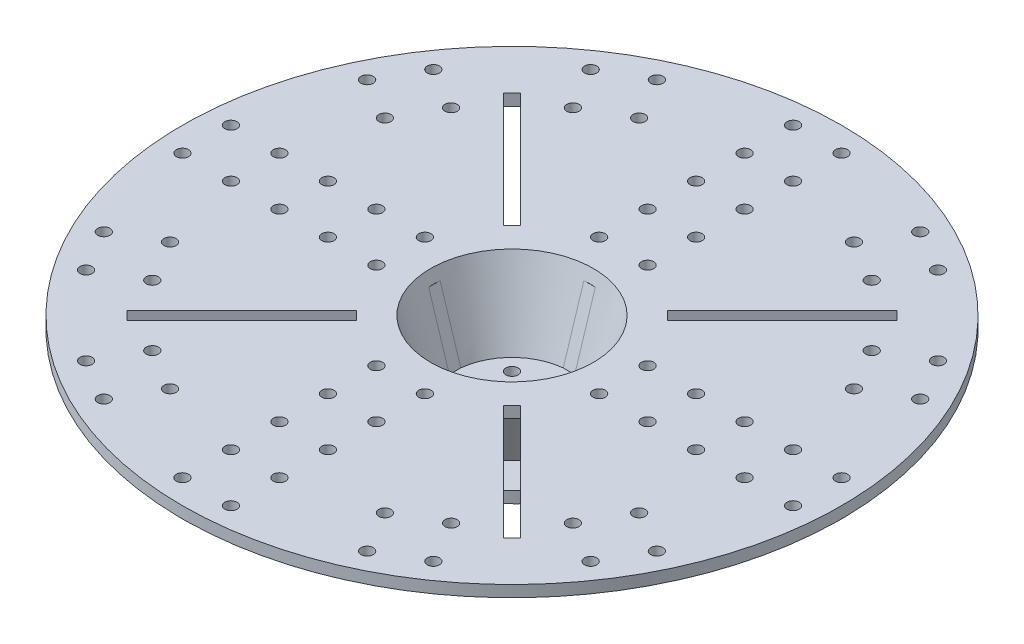
SolidWorks part; units mm, degrees
note: '?' marks a value the reader was unsure of.
material "ULTEM 9085"
ref_plane "Front Plane" through (0, 0, 0) normal (0, 0, 1) x (1, 0, 0)
ref_plane "Top Plane" through (0, 0, 0) normal (0, 1, 0) x (1, 0, 0)
ref_plane "Right Plane" through (0, 0, 0) normal (1, 0, 0) x (0, 0, -1)
other "Center of Mass"
sketch "Sketch1" plane through (0, 0, 0) normal (0, 0, 1) x (1, 0, 0)
  line L0 (0, -40.25) -> (0, -46.25)
  line L1 (0, -40.25) -> (30, -40.25)
  line L2 (30, -40.25) -> (42.6498, 0)
  line L3 (42.6498, 0) -> (172.6498, 0)
  line L4 (105.9574, 0) -> (-105.9574, 0) construction
  line L5 (172.6498, 0) -> (172.6498, -6)
  line L6 (42.6498, 0) -> (42.6498, -31.4331) construction
  line L7 (172.6498, -6) -> (46.8968, -6)
  line L8 (36.1179, -40.2971) -> (46.8968, -6)
  line L9 (36.1179, -40.2971) -> (55.5, -40.2971)
  line L10 (55.5, -40.2971) -> (55.5, -46.25)
  line L11 (55.5, -46.25) -> (0, -46.25)
  line L12 (0, -25.4375) -> (0, 25.4375) construction
  point P15 (0, -43.25)
  point P16 (55.5, -43.2736)
  point P24 (36.3249, -20.125)
  point P25 (41.5074, -23.1486)
  dimension "D1" = 72.553
  dimension "D2" = 30
  dimension "D3" = 130
  dimension "D4" = 6
  dimension "D5" = 6
  dimension "D6" = 55.5
  dimension "D7" = 34.2971
  dimension "D8" = 40.25
  dimension "D9" = 6
revolve "Revolve2" add sketch "Sketch1" angle 360 about L0
ref_axis "Axis1" through (0, 0, 0) along (0, -1, 0)?
sketch "Sketch3" plane through (0, 0, 0) normal (0, 0, 1) x (1, 0, 0)
  line L0 (55.5, -40.2971) -> (172.6498, -6)
  line L1 (172.6498, -6) -> (0, -6)
  line L2 (-172.6498, -6) -> (172.6498, -6) construction
  line L3 (0, -6) -> (0, -40.2971)
  line L4 (55.5, -40.2971) -> (-55.5, -40.2971) construction
  line L5 (0, -40.2971) -> (55.5, -40.2971)
extrude "Boss-Extrude2" add sketch "Sketch3" along normal mid plane 6
pattern_circular "CirPattern2" count 4 over 360 about axis through (0, 0, 0) along (0, 1, 0) of "Boss-Extrude2"
sketch "Sketch6" plane through (0, 0, 3) normal (0, 0, 1) x (1, 0, 0)
  line L0 (-3, -6) -> (-40.6536, -6)
  line L1 (-40.6536, -6) -> (-29.8496, -40.25)
  line L2 (-29.8496, -40.25) -> (-3, -40.25)
  line L3 (-3, -40.25) -> (-3, -6)
  spline S0 degree 3 poles (-29.8496, -40.25) (-33.4553, -28.8347) (-37.0555, -17.4177) (-40.6536, -6) knots 0 0 0 0 1 1 1 1 construction
extrude "Cut-Extrude3" cut sketch "Sketch6" against normal blind 6
pattern_circular "CirPattern4" count 4 over 360 about axis through (0, 0, 0) along (0, 1, 0) of "Cut-Extrude3"
sketch "Sketch7" plane through (0, -6, 0) normal (0, 1, 0) x (1, 0, 0)
  line L0 (-3, 3) -> (-3, -3)
  line L1 (-3, -3) -> (3, -3)
  line L2 (-3, -3) -> (3, -3) construction
  line L3 (3, -3) -> (3, 3)
  line L4 (3, 3) -> (-3, 3) construction
  line L5 (3, 3) -> (-3, 3)
extrude "Cut-Extrude4" cut sketch "Sketch7" against normal up to surface (34.25 mm away) up to face at (0, -40.25, 0)
sketch "Sketch8" plane through (0, -40.25, 0) normal (0, 1, 0) x (1, 0, 0)
  circle A0 centre (0, 0) radius 3.175
  dimension "D1" = 6.35
extrude "Cut-Extrude5" cut sketch "Sketch8" against normal through all
sketch "Sketch11" plane through (0, -6, 0) normal (0, -1, 0) x (1, 0, 0)
  line L0 (0, -25.4375) -> (0, 25.4375) construction
  circle A0 centre (-12.7, 159.9498) radius 3.2
  arc A2 (3, 172.6237) -> (0, 172.6498) centre (0, 0) ccw construction
  point P9 (0, 172.6498)
  dimension "D1" = 6.4
  dimension "D2" = 12.7
  dimension "D3" = 12.7
extrude "Cut-Extrude6" cut sketch "Sketch11" against normal through all
pattern_linear "LPattern2" count 2 spacing 25.4 along (1, 0, 0) count 6 spacing 25.4 along (0, 0, -1) of "Cut-Extrude6"
pattern_circular "CirPattern5" count 4 over 360 about axis through (0, 0, 0) along (0, 1, 0) of "LPattern2", "Cut-Extrude6"
sketch "Sketch12" plane through (0, 0, 0) normal (0, 1, 0) x (1, 0, 0)
  line L0 (0, 0) -> (-149.5191, -86.3249) construction
  line L1 (-25.4375, 0) -> (25.4375, 0) construction
  circle A0 centre (0, 0) radius 172.6498 construction
  dimension "D1" = 30
sketch "Sketch13" plane through (0, 0, 0) normal (0, 1, 0) x (1, 0, 0)
  line L0 (0, 0) -> (149.5191, -86.3249) construction
  line L1 (-25.4375, 0) -> (25.4375, 0) construction
  circle A0 centre (0, 0) radius 172.6498 construction
  dimension "D1" = 30
sketch "Sketch15" plane through (0, 0, 0) normal (0, 1, 0) x (1, 0, 0)
  line L0 (149.5191, -86.3249) -> (115.7369, -144.8374) construction
  line L1 (0, 0) -> (149.5191, -86.3249) construction
  dimension "D1" = 90
sketch "Sketch17" plane through (0, 0, 0) normal (0, 1, 0) x (1, 0, 0)
  line L0 (0, 0) -> (149.5191, -86.3249) construction
  line L1 (149.5191, -86.3249) -> (115.7369, -144.8374) construction
  circle A0 centre (132.1706, -90.9734) radius 3.2
  dimension "D1" = 6.4
  dimension "D2" = 12.7
  dimension "D3" = 12.7
extrude "Cut-Extrude7" cut sketch "Sketch17" against normal through all
pattern_linear "LPattern3" count 2 spacing 25.4 along (-0.866, 0, -0.5) count 2 spacing 25.4 along (0.5, 0, -0.866) of "Cut-Extrude7"
mirror "Mirror1" about plane through (0, 0, 0) normal (1, 0, 0) of "LPattern3", "Cut-Extrude7"
mirror "Mirror2" about plane through (0, 0, 0) normal (0, 0, 1) of "Mirror1", "Cut-Extrude7", "LPattern3"
sketch "Sketch18" plane through (0, 0, 0) normal (0, 1, 0) x (1, 0, 0)
  line L0 (0, 0) -> (122.0818, 122.0818) construction
  line L1 (-25.4375, 0) -> (25.4375, 0) construction
  circle A0 centre (0, 0) radius 172.6498 construction
  dimension "D1" = 45
sketch "Sketch19" plane through (0, 0, 0) normal (0, 1, 0) x (1, 0, 0)
  line L0 (103.1314, 98.6059) -> (98.6059, 103.1314)
  line L1 (103.1314, 98.6059) -> (43.0273, 38.5018)
  line L2 (98.6059, 103.1314) -> (38.5018, 43.0273)
  line L3 (43.0273, 38.5018) -> (38.5018, 43.0273)
  line L5 (0, 0) -> (122.0818, 122.0818) construction
  point P6 (100.8686, 100.8686)
  dimension "D1" = 3.2
  dimension "D2" = 6.4
  dimension "D3" = 85
  dimension "D4" = 30
extrude "Cut-Extrude8" cut sketch "Sketch19" against normal up to next
pattern_circular "CirPattern6" count 4 over 360 about axis through (0, 0, 0) along (0, 1, 0) of "Cut-Extrude8"
sketch "Sketch23" plane through (0, -46.25, 0) normal (0, -1, 0) x (1, 0, 0)
  line L0 (23, -39.8372) -> (0, 0) construction
  line L1 (0, -25.4375) -> (0, 25.4375) construction
  circle A0 centre (23, -39.8372) radius 3.2
  dimension "D1" = 6.4
  dimension "D3" = 30
  dimension "D2" = 46
extrude "Cut-Extrude9" cut sketch "Sketch23" along direction (0, 1, 0) on the side against the normal up to next (5.9529 mm away)
pattern_circular "CirPattern7" count 2 every 30 about axis through (0, 0, 0) along (0, -1, 0) of "Cut-Extrude9"
pattern_circular "CirPattern8" count 4 over 360 about axis through (0, 0, 0) along (0, 1, 0) of "CirPattern7", "Cut-Extrude9"
sketch "Sketch24" plane through (0, 0, 0) normal (0, 1, 0) x (1, 0, 0)
  line L0 (86.3249, -149.5191) -> (0, 0) construction
  line L1 (0, -25.4375) -> (0, 25.4375) construction
  circle A0 centre (0, 0) radius 172.6498 construction
  dimension "D1" = 30
sketch "Sketch25" plane through (0, 0, 0) normal (0, 1, 0) x (1, 0, 0)
  line L0 (86.3249, -149.5191) -> (54.8663, -167.6817) construction
  line L1 (86.3249, -149.5191) -> (0, 0) construction
  dimension "D1" = 90
sketch "Sketch26" plane through (0, 0, 0) normal (0, 1, 0) x (1, 0, 0)
  line L0 (86.3249, -149.5191) -> (54.8663, -167.6817) construction
  line L1 (86.3249, -149.5191) -> (0, 0) construction
  circle A0 centre (68.9764, -144.8706) radius 3.2
  dimension "D1" = 6.4
  dimension "D2" = 12.7
  dimension "D3" = 12.7
extrude "Cut-Extrude10" cut sketch "Sketch26" against normal through all
pattern_linear "LPattern4" count 2 spacing 25.4 along (-0.5, 0, -0.866) count 2 spacing 25.4 along (0.866, 0, -0.5) of "Cut-Extrude10"
mirror "Mirror3" about plane through (0, 0, 0) normal (1, 0, 0) of "LPattern4", "Cut-Extrude10"
mirror "Mirror4" about plane through (0, 0, 0) normal (0, 0, 1) of "Mirror3", "Cut-Extrude10", "LPattern4"
sketch "Sketch27" plane through (0, -46.25, 0) normal (0, -1, 0) x (1, 0, 0)
  line L0 (0, 0) -> (122.0818, -122.0818) construction
  circle A0 centre (14.8492, -14.8492) radius 3.2
  dimension "D1" = 6.4
  dimension "D2" = 21
extrude "Cut-Extrude11" cut sketch "Sketch27" against normal up to next
pattern_circular "CirPattern9" count 4 over 360 about axis through (0, 0, 0) along (0, 1, 0) of "Cut-Extrude11"
sketch "Sketch28" plane through (3, 0, 0) normal (1, 0, 0) x (0, 0, -1)
  line L0 (0, 25.4375) -> (0, -25.4375) construction
  line L1 (51, -12.4) -> (101, -12.4)
  line L2 (51, -12.4) -> (51, -18.8)
  line L3 (51, -18.8) -> (101, -18.8)
  line L4 (101, -12.4) -> (101, -18.8)
  line L5 (3, -6) -> (172.6237, -6) construction
  dimension "D1" = 6.4
  dimension "D2" = 51
  dimension "D3" = 6.4
  dimension "D4" = 50
extrude "Cut-Extrude12" cut sketch "Sketch28" against normal up to next
pattern_circular "CirPattern10" count 4 over 360 about axis through (0, 0, 0) along (0, 1, 0) of "Cut-Extrude12"
